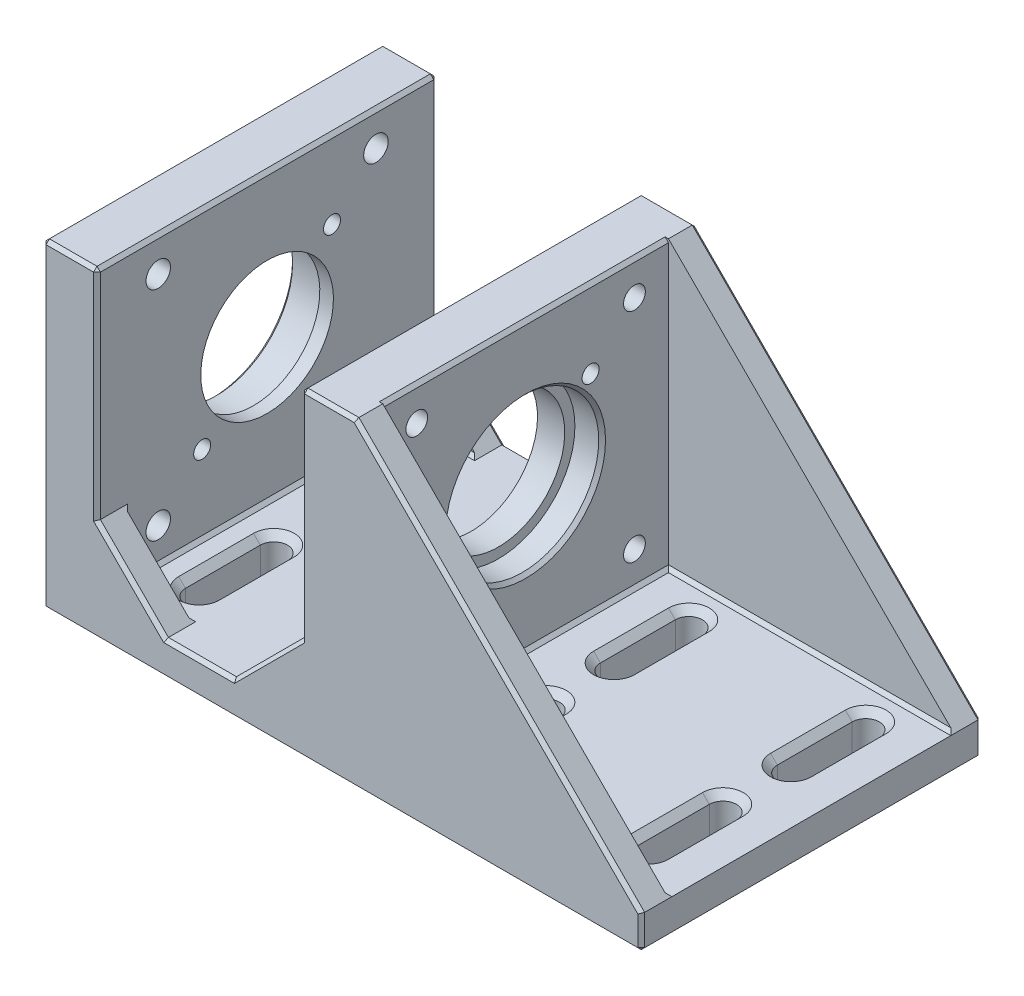
SolidWorks part; units mm, degrees
ref_plane "Front Plane" through (0, 0, 0) normal (0, 0, 1) x (1, 0, 0)
ref_plane "Top Plane" through (0, 0, 0) normal (0, 1, 0) x (1, 0, 0)
ref_plane "Right Plane" through (0, 0, 0) normal (1, 0, 0) x (0, 0, -1)
sketch "Sketch1" plane through (0, 0, 0) normal (0, 0, 1) x (1, 0, 0)
  line L0 (-8, 21) -> (-8, -11)
  line L1 (-18, -21) -> (-28, -21)
  line L2 (-38, -11) -> (-38, 21)
  line L3 (-38, 21) -> (-46, 21)
  line L4 (-46, 21) -> (-46, -26)
  line L5 (-46, -26) -> (42, -26)
  line L6 (42, -26) -> (42, -21)
  line L8 (42, -21) -> (0, 21)
  line L9 (0, 21) -> (-8, 21)
  line L10 (-28, -21) -> (-38, -11)
  line L11 (-8, -11) -> (-18, -21)
  point P1 (-8, -21)
  point P3 (-38, -21)
  dimension "D1" = 42
  dimension "D2" = 30
  dimension "D3" = 5
  dimension "D4" = 8
  dimension "D5" = 8
  dimension "D6" = 45
  dimension "D7" = 21
extrude "Boss-Extrude1" add sketch "Sketch1" along normal mid plane 50
sketch "Sketch2" plane through (0, 0, 0) normal (0, 0, 1) x (1, 0, 0)
  line L0 (-38, 21) -> (-38, -21)
  line L1 (-38, -21) -> (-8, -21)
  line L2 (-8, -21) -> (-8, 21)
  line L3 (-18, -21) -> (-28, -21) construction
  line L4 (-8, 21) -> (-38, 21)
  line L5 (0, 21) -> (0, -21)
  line L6 (0, -21) -> (42, -21)
  line L7 (42, -21) -> (0, 21)
extrude "Cut-Extrude1" cut sketch "Sketch2" along normal offset from surface 4 and the other way offset from surface 4 up to face at (-13.2727, -4.8182, 25) other way up to face at (-13.2727, -4.8182, -25)
sketch "Sketch3" plane through (0, 0, 0) normal (1, 0, 0) x (0, 0, -1)
  circle A0 centre (0, 0) radius 11.25
  dimension "D1" = 22.5
extrude "Cut-Extrude2" cut sketch "Sketch3" against normal through all both and the other way through all
sketch "Sketch4" plane through (-38, 0, 0) normal (-1, 0, 0) x (0, 0, 1)
  circle A1 centre (0, 0) radius 11.25 construction
  circle A2 centre (0, 0) radius 9.75
  circle A3 centre (0, 0) radius 9.75
  circle A4 centre (0, 0) radius 11.25
  dimension "D1" = 1.5
extrude "Boss-Extrude2" add sketch "Sketch4" along normal blind 2
hole_wizard "Tap Drill for M3x0.5 Tap1" positions "Sketch8" profile "Sketch10" hole size "M3x0.5" standard "ANSI Metric" end condition through all
sketch "Sketch8" plane through (-46, 0, 0) normal (-1, 0, 0) x (0, 0, 1)
  line L0 (-9.5459, 9.5459) -> (9.5459, -9.5459)
  line L2 (25, 21) -> (-25, 21) construction
  point P0 (-9.5459, 9.5459)
  point P2 (9.5459, -9.5459)
  point P11 (0, 0)
  dimension "D1" = 45
  dimension "D2" = 27
sketch "Sketch10" plane through (-46, 9.5459, -9.5459) normal (0, 1, 0) x (0, 0, 1)
  line L0 (0, 0) -> (0, 88)
  line L1 (0, 88) -> (1.25, 88)
  line L2 (1.25, 88) -> (1.25, 0)
  line L5 (1.25, 0) -> (0, 0)
  line L11 (0, -6.35) -> (0, 107.95) construction
  dimension "Thru Hole Dia." = 2.5
  dimension "Thru Hole Depth" = 88
hole_wizard "CSK for M3 Flat Head Machine Screw1" positions "Sketch12" profile "Sketch13" countersink size "M3" standard "ANSI Metric" end condition up to next
sketch "Sketch12" plane through (-8, 0, 0) normal (-1, 0, 0) x (0, 0, 1)
  line L1 (16, -16) -> (-16, -16) construction
  line L2 (16, -16) -> (16, 16) construction
  line L3 (16, 16) -> (-16, 16) construction
  line L4 (-16, -16) -> (-16, 16) construction
  line L5 (16, -16) -> (-16, 16) construction
  line L6 (16, 16) -> (-16, -16) construction
  point P0 (-16, 16)
  point P2 (16, 16)
  point P4 (16, -16)
  point P6 (-16, -16)
  point P9 (0, 0)
  dimension "D1" = 32
sketch "Sketch13" plane through (-8, 16, -16) normal (0, 1, 0) x (0, 0, 1)
  line L0 (0, 0) -> (0, 8)
  line L1 (0, 8) -> (1.6, 8)
  line L2 (1.6, 8) -> (1.6, 1.55)
  line L3 (1.6, 1.55) -> (3.15, 0)
  line L5 (3.15, 0) -> (0, 0)
  line L6 (-1.6, 1.55) -> (-3.15, 0) construction
  line L11 (0, -6.35) -> (0, 107.95) construction
  dimension "Thru Hole Dia." = 3.2
  dimension "Thru Hole Depth" = 8
  dimension "Near C'Sink Dia." = 6.3
  dimension "Near C'Sink Angle" = 90
chamfer "Chamfer1" distance 0.5 angle 45 43 edges at (0, 0, -11.25) (-46, 0, -11.25) (-8, -16, -21) (-8, -16, 21) (-13, -21, 21) (-8, -21, 0) (-13, -21, -21) (-38, -16, 21) (-38, -16, -21) (-33, -21, -21) (-38, -21, 0) (-33, -21, 21) (21, -21, 21) (0, -21, 0) (21, -21, -21) (0, 21, 0) (-8, 21, 0) (-4, 21, 25) (-8, 5, 25) (-13, -16, 25) (-23, -21, 25) (-33, -16, 25) (-38, 5, 25) (-42, 21, 25) (-38, 21, 0) (-46, 21, 0) (-42, 21, -25) (-38, 5, -25) (-33, -16, -25) (-23, -21, -25) (-13, -16, -25) (-8, 5, -25) (-4, 21, -25) (21, 0, 25) (21, 0, -25) (42, -23.5, 25) (42, -23.5, -25) (-46, -2.5, -25) (-46, -2.5, 25) (42, -26, 0) (-2, -26, -25) (-46, -26, 0) (-2, -26, 25)
extrude "Boss-Extrude3" add sketch "Sketch4<2>" against normal blind 4 from surface starting at face at (-8, -5.5, 0)
sketch "Sketch4<2>" plane through (-38, 0, 0) normal (-1, 0, 0) x (0, 0, 1) same geometry as "Sketch4"
hole_wizard "M3 Clearance Hole1" positions "Sketch18" profile "Sketch17" hole size "M3" standard "ANSI Metric" end condition up to next
sketch "Sketch18" plane through (-46, 0, 0) normal (-1, 0, 0) x (0, 0, 1)
  circle A0 centre (-16, -16) radius 1.6 construction
  circle A1 centre (16, -16) radius 1.6 construction
  circle A2 centre (16, 16) radius 1.6 construction
  circle A3 centre (-16, 16) radius 1.6 construction
  circle A4 centre (-16, -16) radius 1.6
  circle A5 centre (16, -16) radius 1.6
  circle A6 centre (16, 16) radius 1.6
  circle A7 centre (-16, 16) radius 1.6
  point P1 (-16, -16)
  point P3 (16, -16)
  point P5 (16, 16)
  point P7 (-16, 16)
sketch "Sketch17" plane through (-46, -16, -16) normal (0, 1, 0) x (0, 0, 1)
  line L0 (0, 0) -> (0, 8)
  line L1 (0, 8) -> (1.8, 8)
  line L2 (1.8, 8) -> (1.8, 0)
  line L5 (1.8, 0) -> (0, 0)
  line L11 (0, -6.35) -> (0, 107.95) construction
  dimension "Thru Hole Dia." = 3.6
  dimension "Thru Hole Depth" = 8
sketch "Sketch19" plane through (0, -21, 0) normal (0, 1, 0) x (1, 0, 0)
  line L0 (-32, 5) -> (-32, 16) construction
  line L1 (-34, 5) -> (-34, 16)
  line L2 (-30, 5) -> (-30, 16)
  line L3 (-14, 5) -> (-14, 16) construction
  line L4 (-16, 5) -> (-16, 16)
  line L5 (-12, 5) -> (-12, 16)
  line L6 (-17.5, 21) -> (-8.5, 21) construction
  line L7 (-38, -20.5) -> (-38, 20.5) construction
  line L8 (-8, -24.5) -> (-8, 24.5) construction
  line L9 (8, 5) -> (8, 16) construction
  line L10 (6, 5) -> (6, 16)
  line L11 (10, 5) -> (10, 16)
  line L12 (34, 5) -> (34, 16) construction
  line L13 (32, 5) -> (32, 16)
  line L14 (36, 5) -> (36, 16)
  line L16 (0, -21) -> (0, 21) construction
  line L17 (42, -20.5) -> (42, 20.5) construction
  arc A0 (-34, 5) -> (-30, 5) centre (-32, 5) ccw
  arc A1 (-30, 16) -> (-34, 16) centre (-32, 16) ccw
  arc A2 (-16, 5) -> (-12, 5) centre (-14, 5) ccw
  arc A3 (-12, 16) -> (-16, 16) centre (-14, 16) ccw
  arc A4 (6, 5) -> (10, 5) centre (8, 5) ccw
  arc A5 (10, 16) -> (6, 16) centre (8, 16) ccw
  arc A6 (32, 5) -> (36, 5) centre (34, 5) ccw
  arc A7 (36, 16) -> (32, 16) centre (34, 16) ccw
  point P2 (-32, 10.5)
  point P7 (-14, 10.5)
  point P21 (8, 10.5)
  point P28 (34, 10.5)
  point P39 (0, 0)
  dimension "D3" = 2
  dimension "D1" = 5
  dimension "D2" = 5
  dimension "D4" = 6
  dimension "D5" = 6
  dimension "D6" = 8
  dimension "D7" = 8
extrude "Cut-Extrude3" cut sketch "Sketch19" against normal through all
chamfer "Chamfer2" distance 1 angle 45 16 edges at (36, -21, -10.5) (34, -21, -18) (34, -21, -3) (32, -21, -10.5) (10, -21, -10.5) (8, -21, -18) (8, -21, -3) (6, -21, -10.5) (-12, -21, -10.5) (-14, -21, -18) (-14, -21, -3) (-16, -21, -10.5) (-34, -21, -10.5) (-32, -21, -3) (-32, -21, -18) (-30, -21, -10.5)
mirror "Mirror1" about plane through (0, 0, 0) normal (0, 0, 1) of "Chamfer2", "Cut-Extrude3"
